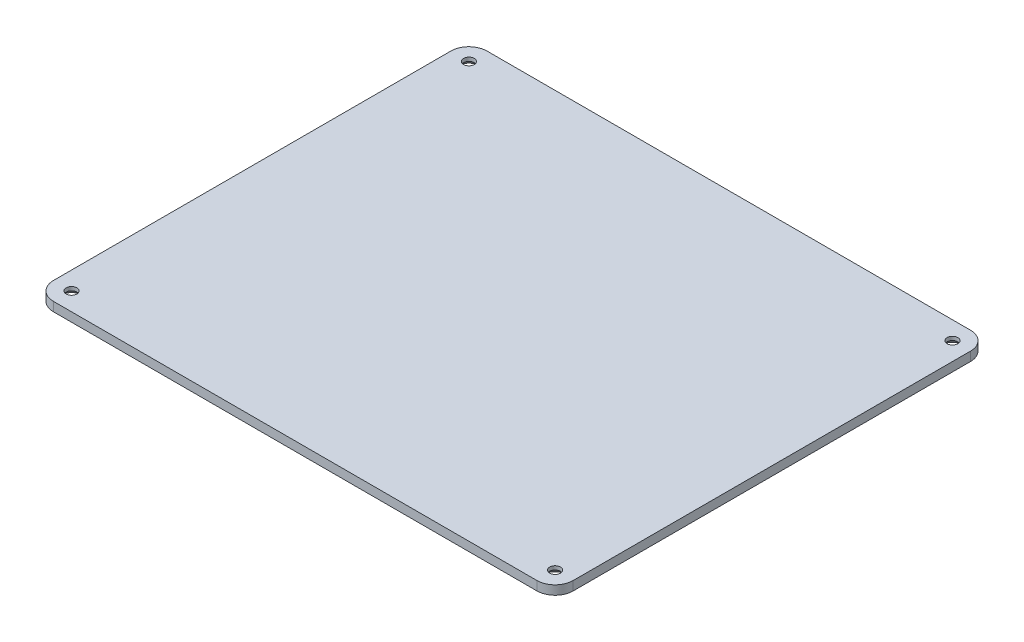
SolidWorks part; units mm, degrees
material "ABS"
ref_plane "Front" through (0, 0, 0) normal (0, 0, 1) x (1, 0, 0)
ref_plane "Top" through (0, 0, 0) normal (0, 1, 0) x (1, 0, 0)
ref_plane "Right" through (0, 0, 0) normal (1, 0, 0) x (0, 0, -1)
sketch "Sketch1" plane through (0, 0, 0) normal (0, 1, 0) x (1, 0, 0)
  line L1 (-43.1005, 35.9565) -> (43.1005, 35.9565)
  line L2 (-43.1005, 35.9565) -> (-43.1005, -35.9565)
  line L3 (-43.1005, -35.9565) -> (43.1005, -35.9565)
  line L4 (43.1005, 35.9565) -> (43.1005, -35.9565)
  line L5 (-43.1005, 35.9565) -> (43.1005, -35.9565) construction
  line L6 (-43.1005, -35.9565) -> (43.1005, 35.9565) construction
  point P0 (0, 0)
  dimension "D1" = 71.913
  dimension "D2" = 86.201
extrude "Boss-Extrude1" add sketch "Sketch1" along normal blind 1.5
fillet "Fillet1" radius 3 4 edges at (-43.1005, 0.75, 35.9565) (-43.1005, 0.75, -35.9565) (43.1005, 0.75, -35.9565) (43.1005, 0.75, 35.9565)
hole_wizard "#2-56 Tapped Hole1" positions "Sketch2" profile "Sketch4" tap size "#2-56" standard "ANSI Inch" end condition through all
sketch "Sketch2" plane through (0, 0, 0) normal (0, -1, 0) x (-1, 0, 0)
  point P0 (40.1005, -32.9565)
  point P3 (-40.1005, -32.9565)
  point P6 (-40.1005, 32.9565)
  point P9 (40.1005, 32.9565)
sketch "Sketch4" plane through (-40.1005, 0, 32.9565) normal (1, 0, 0) x (0, 0, -1)
  line L0 (0, 0) -> (0, 1.5)
  line L1 (0, 1.5) -> (0.889, 1.5)
  line L2 (0.889, 1.5) -> (0.889, 0.889)
  line L3 (0.889, 0.889) -> (1.778, 0)
  line L5 (1.778, 0) -> (0, 0)
  line L6 (-0.889, 0.889) -> (-1.778, 0) construction
  line L11 (0, -6.35) -> (0, 107.95) construction
  dimension "Thru Tap Drill Dia." = 1.778
  dimension "Thru Tap Drill Depth" = 1.5
  dimension "Near C'Sink Dia." = 3.556
  dimension "Near C'Sink Angle" = 90
cosmetic thread "Hole Thread1" parameters "D2"=2.1844
cosmetic thread "Hole Thread2" parameters "D2"=2.1844
cosmetic thread "Hole Thread3" parameters "D2"=2.1844
cosmetic thread "Hole Thread4" parameters "D2"=2.1844
